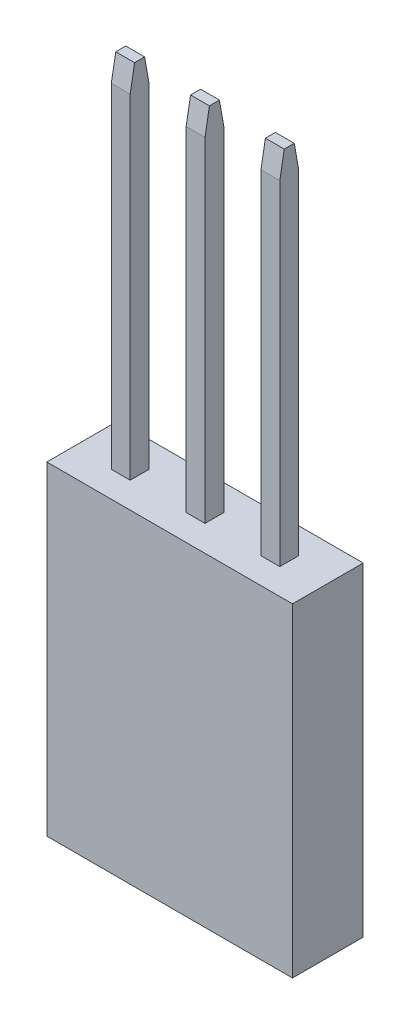
SolidWorks part; units mm, degrees
ref_plane "Front Plane" through (0, 0, 0) normal (0, 0, 1) x (1, 0, 0)
ref_plane "Top Plane" through (0, 0, 0) normal (0, 1, 0) x (1, 0, 0)
ref_plane "Right Plane" through (0, 0, 0) normal (1, 0, 0) x (0, 0, -1)
sketch "Sketch1" plane through (0, 0, 0) normal (0, 1, 0) x (1, 0, 0)
  line L0 (-2.54, 0) -> (2.54, 0) construction
  line L1 (-4.17, 1.2) -> (4.17, 1.2)
  line L2 (-4.17, 1.2) -> (-4.17, -1.2)
  line L3 (-4.17, -1.2) -> (4.17, -1.2)
  line L4 (4.17, 1.2) -> (4.17, -1.2)
  point P4 (0, -1.2)
  point P6 (4.17, 0)
  point P7 (-2.54, 0)
  point P8 (0, 0)
  point P9 (2.54, 0)
  dimension "D1" = 2.4
  dimension "D2" = 2.54
  dimension "D4" = 8.34
extrude "Boss-Extrude1" add sketch "Sketch1" against normal blind 11
sketch "Sketch2" plane through (0, 0, 0) normal (0, 1, 0) x (1, 0, 0)
  line L0 (0, 0.32) -> (0, -0.32) construction
  line L1 (-0.32, 0.32) -> (0.32, 0.32)
  line L2 (-0.32, 0.32) -> (-0.32, -0.32)
  line L3 (-0.32, -0.32) -> (0.32, -0.32)
  line L4 (0.32, 0.32) -> (0.32, -0.32)
  line L5 (-2.86, 0.32) -> (-2.22, 0.32)
  line L6 (-2.86, 0.32) -> (-2.86, -0.32)
  line L7 (-2.86, -0.32) -> (-2.22, -0.32)
  line L8 (-2.22, 0.32) -> (-2.22, -0.32)
  line L9 (2.22, 0.32) -> (2.22, -0.32)
  line L10 (2.86, -0.32) -> (2.22, -0.32)
  line L11 (2.86, 0.32) -> (2.86, -0.32)
  line L12 (2.86, 0.32) -> (2.22, 0.32)
  point P4 (0.32, 0)
  point P6 (0, 0.32)
  point P11 (-2.54, 0.32)
  point P13 (-2.22, 0)
  dimension "D1" = 0.64
  dimension "D2" = 0.64
extrude "Boss-Extrude2" add sketch "Sketch2" along normal blind 12.2 separate body
chamfer "Chamfer1" distance 0.15 angle 80 2 edges at (-2.54, 12.2, -0.32) (-2.54, 12.2, 0.32) first distance on face at (-2.54, 12.2, 0)
chamfer "Chamfer2" distance 0.15 angle 80 2 edges at (0, 12.2, -0.32) (0, 12.2, 0.32) first distance on face at (0, 12.2, 0)
chamfer "Chamfer3" distance 0.15 angle 80 2 edges at (2.54, 12.2, -0.32) (2.54, 12.2, 0.32) first distance on face at (2.54, 12.2, 0)
extrude "Cut-Extrude1" cut sketch "Sketch2<2>" along normal blind 4 from surface starting at face at (0, -11, 0)
sketch "Sketch2<2>" plane through (0, 0, 0) normal (0, 1, 0) x (1, 0, 0) same geometry as "Sketch2"
chamfer "Chamfer4" distance 0.3 angle 45 12 edges at (-2.54, -11, -0.32) (-2.22, -11, 0) (-2.54, -11, 0.32) (-2.86, -11, 0) (0.32, -11, 0) (0, -11, -0.32) (-0.32, -11, 0) (0, -11, 0.32) (2.86, -11, 0) (2.54, -11, -0.32) (2.22, -11, 0) (2.54, -11, 0.32)
